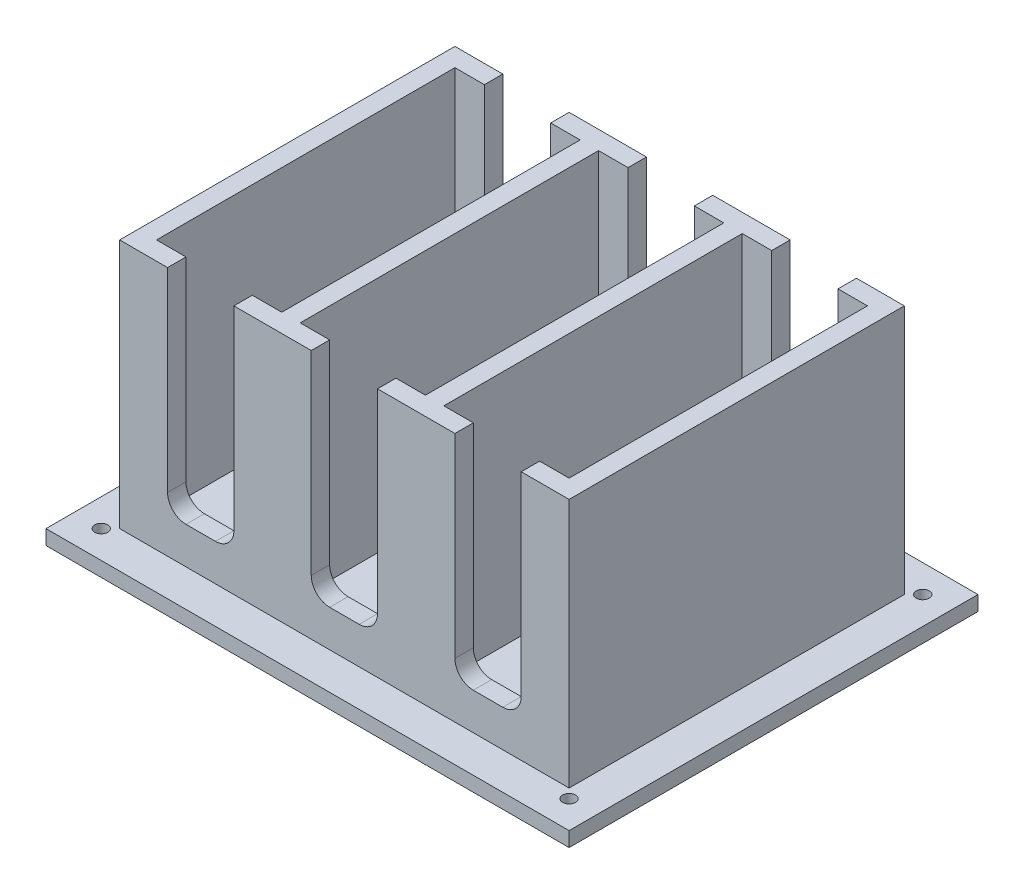
SolidWorks part; units mm, degrees
ref_plane "Front Plane" through (0, 0, 0) normal (0, 0, 1) x (1, 0, 0)
ref_plane "Top Plane" through (0, 0, 0) normal (0, 1, 0) x (1, 0, 0)
ref_plane "Right Plane" through (0, 0, 0) normal (1, 0, 0) x (0, 0, -1)
sketch "Sketch1" plane through (0, 0, 0) normal (0, 1, 0) x (1, 0, 0)
  line L1 (22, -40.5) -> (56, -40.5) construction
  line L2 (22, -40.5) -> (22, 40.5) construction
  line L3 (22, 40.5) -> (56, 40.5) construction
  line L4 (56, -40.5) -> (56, 40.5) construction
  line L5 (22, -40.5) -> (56, 40.5) construction
  line L6 (22, 40.5) -> (56, -40.5) construction
  line L10 (-17, 40.5) -> (17, 40.5) construction
  line L11 (-77.056, 0) -> (77.056, 0) construction
  line L12 (0, -60.8091) -> (0, 60.8091) construction
  line L13 (-71, 55.5) -> (71, -55.5) construction
  line L14 (-17, -40.5) -> (-17, 40.5) construction
  line L15 (17, -40.5) -> (17, 40.5) construction
  line L16 (-17, -40.5) -> (17, -40.5) construction
  line L17 (-56, 40.5) -> (-22, 40.5) construction
  line L18 (-56, -40.5) -> (-56, 40.5) construction
  line L19 (-22, -40.5) -> (-22, 40.5) construction
  line L20 (-56, -40.5) -> (-22, -40.5) construction
  line L21 (-17, 40.5) -> (17, -40.5) construction
  line L23 (-71, -55.5) -> (71, -55.5)
  line L24 (-71, -55.5) -> (-71, 55.5)
  line L25 (-71, 55.5) -> (71, 55.5)
  line L26 (71, -55.5) -> (71, 55.5)
  line L27 (-71, 55.5) -> (-56, 40.5) construction
  circle A0 centre (-63.5, 48) radius 1.75
  circle A1 centre (-63.5, -48) radius 1.75
  circle A2 centre (63.5, 48) radius 1.75
  circle A3 centre (63.5, -48) radius 1.75
  point P0 (39, 0)
  point P5 (0, 0)
  dimension "D4" = 3.5
  dimension "D5" = 3
  dimension "D1" = 34
  dimension "D2" = 81
  dimension "D6" = 5
  dimension "D7" = 15
  dimension "D3" = 15
extrude "Boss-Extrude1" add sketch "Sketch1" along normal blind 4
sketch "Sketch5" plane through (0, 4, 0) normal (0, 1, 0) x (1, 0, 0)
  line L0 (-56, -40.5) -> (-56, 40.5)
  line L1 (-9, 45.5) -> (-9, 40.5)
  line L2 (-56, -40.5) -> (-48, -40.5)
  line L3 (-56, -40.5) -> (-22, -40.5) construction
  line L4 (-48, -40.5) -> (-48, -45.5)
  line L5 (-48, -45.5) -> (-61, -45.5)
  line L6 (-61, -45.5) -> (-61, 45.5)
  line L7 (-61, 45.5) -> (-48, 45.5)
  line L8 (-48, 45.5) -> (-48, 40.5)
  line L9 (-56, 40.5) -> (-22, 40.5) construction
  line L10 (-48, 40.5) -> (-56, 40.5)
  line L11 (-56, -40.5) -> (-61, -40.5) construction
  line L28 (-22, 40.5) -> (-30, 40.5)
  line L29 (-30, 40.5) -> (-30, 45.5)
  line L30 (-30, 45.5) -> (-9, 45.5)
  line L31 (-77.056, 0) -> (77.056, 0) construction
  line L32 (-22, -40.5) -> (-30, -40.5)
  line L33 (-30, -40.5) -> (-30, -45.5)
  line L34 (-30, -45.5) -> (-9, -45.5)
  line L35 (-17, 40.5) -> (17, 40.5) construction
  line L36 (-9, 40.5) -> (-17, 40.5)
  line L37 (-17, 40.5) -> (-17, -40.5)
  line L38 (-17, -40.5) -> (-9, -40.5)
  line L39 (-17, -40.5) -> (17, -40.5) construction
  line L40 (-9, -40.5) -> (-9, -45.5)
  line L41 (-22, -40.5) -> (-22, 40.5)
  line L42 (17, -40.5) -> (17, 40.5)
  line L43 (17, 40.5) -> (9, 40.5)
  line L44 (9, 40.5) -> (9, 45.5)
  line L45 (9, 45.5) -> (30, 45.5)
  line L46 (30, 45.5) -> (30, 40.5)
  line L47 (30, 40.5) -> (22, 40.5)
  line L48 (22, 40.5) -> (22, -40.5)
  line L49 (22, -40.5) -> (30, -40.5)
  line L50 (30, -40.5) -> (30, -45.5)
  line L51 (9, -45.5) -> (30, -45.5)
  line L52 (9, -40.5) -> (9, -45.5)
  line L53 (17, -40.5) -> (9, -40.5)
  line L54 (56, -40.5) -> (56, 40.5)
  line L55 (56, 40.5) -> (48, 40.5)
  line L56 (48, 40.5) -> (48, 45.5)
  line L57 (48, 45.5) -> (61, 45.5)
  line L60 (61, 40.5) -> (61, -40.5)
  line L63 (48, -45.5) -> (61, -45.5)
  line L64 (48, -40.5) -> (48, -45.5)
  line L65 (56, -40.5) -> (48, -40.5)
  line L66 (69, 45.5) -> (69, 40.5) [skipped]
  line L67 (69, 40.5) -> (61, 40.5) [skipped]
  line L68 (61, 40.5) -> (61, 45.5)
  line L69 (61, -40.5) -> (61, -45.5)
  line L71 (61, -40.5) -> (69, -40.5) [skipped]
  line L72 (69, -40.5) -> (69, -45.5) [skipped]
  dimension "D1" = 5
  dimension "D2" = 8
  dimension "D3" = 8
  dimension "D4" = 3
extrude "Boss-Extrude3" add sketch "Sketch5" along normal blind 67.862
sketch "Sketch6" plane through (0, 4, 0) normal (0, 1, 0) x (1, 0, 0)
  line L1 (-61, -45.5) -> (61, -45.5)
  line L2 (-61, -45.5) -> (-61, 45.5)
  line L3 (-61, 45.5) -> (61, 45.5)
  line L4 (61, -45.5) -> (61, 45.5)
  line L5 (-56, -40.5) -> (56, -40.5)
  line L6 (-56, -40.5) -> (-56, 40.5)
  line L7 (-56, 40.5) -> (56, 40.5)
  line L8 (56, -40.5) -> (56, 40.5)
extrude "Boss-Extrude4" add sketch "Sketch6" along normal blind 10
fillet "Fillet1" radius 5 12 edges at (-30, 14, -43) (-48, 14, -43) (-9, 14, -43) (9, 14, -43) (30, 14, -43) (48, 14, -43) (48, 14, 43) (30, 14, 43) (-9, 14, 43) (9, 14, 43) (-48, 14, 43) (-30, 14, 43)
sketch "Sketch7" plane through (0, 4, 0) normal (0, 1, 0) x (1, 0, 0)
  line L0 (-56, 40.5) -> (-22, 40.5) construction
  line L1 (-56, -40.5) -> (-31.5, -40.5)
  line L2 (-56, -40.5) -> (-56, 40.5)
  line L3 (-56, 40.5) -> (-31.5, 40.5)
  line L4 (-31.5, -40.5) -> (-31.5, 40.5)
  line L5 (-22, -40.5) -> (-22, 40.5) construction
  line L6 (-17, -40.5) -> (-17, 40.5)
  line L7 (-17, -40.5) -> (7.5, -40.5)
  line L8 (7.5, -40.5) -> (7.5, 40.5)
  line L9 (-17, 40.5) -> (7.5, 40.5)
  line L10 (22, -40.5) -> (22, 40.5)
  line L11 (22, -40.5) -> (46.5, -40.5)
  line L12 (46.5, -40.5) -> (46.5, 40.5)
  line L13 (22, 40.5) -> (46.5, 40.5)
  point P9 (-16.6836, -40.281)
  dimension "D1" = 9.5
  dimension "D2" = 3
extrude "Boss-Extrude5" add sketch "Sketch7" along normal blind 3.2885
